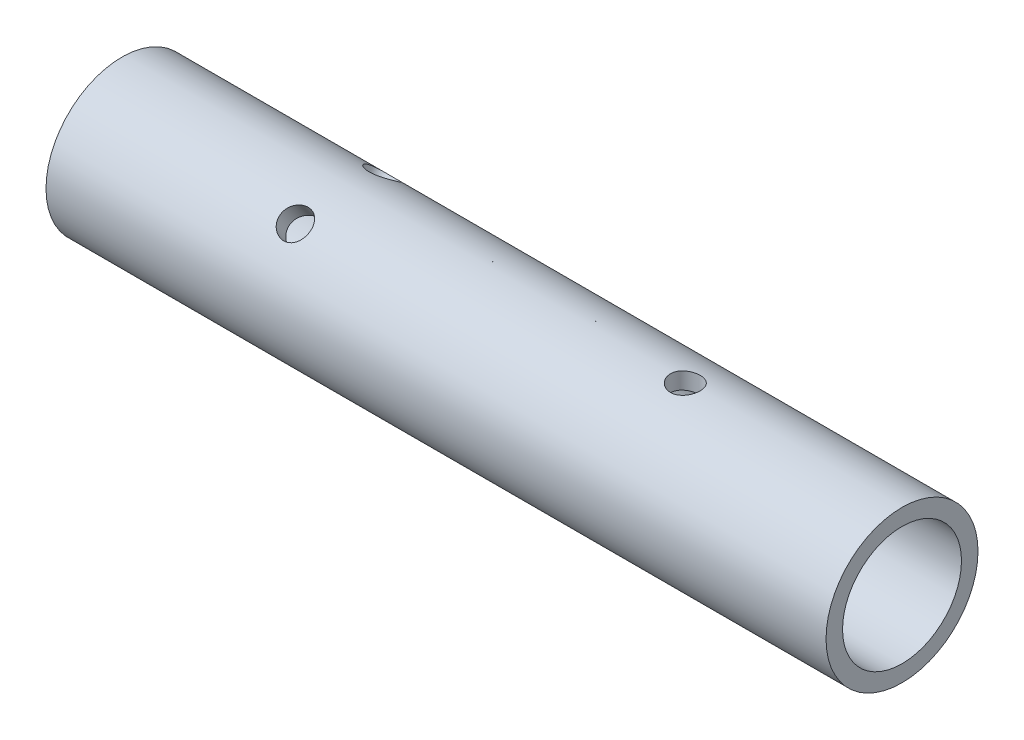
SolidWorks part; units mm, degrees
ref_plane "Front Plane" through (0, 0, 0) normal (0, 0, 1) x (1, 0, 0)
ref_plane "Top Plane" through (0, 0, 0) normal (0, 1, 0) x (1, 0, 0)
ref_plane "Right Plane" through (0, 0, 0) normal (1, 0, 0) x (0, 0, -1)
sketch "Sketch1" plane through (0, 0, 0) normal (1, 0, 0) x (0, 0, -1)
  circle A0 centre (0, 0) radius 16.7005
  circle A1 centre (0, 0) radius 13.0683
  dimension "D1" = 33.401
  dimension "D2" = 26.1366
extrude "Boss-Extrude1" add sketch "Sketch1" along normal blind 254
sketch "Sketch3" plane through (0, 0, 0) normal (0, 1, 0) x (1, 0, 0)
  line L0 (127, 16.7005) -> (127, -16.7005) construction
  line L1 (254, 16.7005) -> (0, 16.7005) construction
  line L2 (0, -16.7005) -> (254, -16.7005) construction
  circle A0 centre (127, 0) radius 3.2639
  dimension "D1" = 6.5278
extrude "Cut-Extrude2" cut sketch "Sketch3" against normal through all both and the other way through all
ref_axis "Axis1" through (254, 0, 0) along (-1, 0, 0)
ref_plane "Plane1" through (0, 0, 0) normal (0, 0.8192, -0.5736) x (-1, 0, 0)
sketch "Sketch4" plane through (0, 0, 0) normal (0, 0.8192, -0.5736) x (-1, 0, 0)
  line L0 (-254, 0) -> (-203.2, 0) construction
  line L1 (-254, 16.7005) -> (-254, -16.7005) construction
  line L2 (-254, 0) -> (0, 0) construction
  line L3 (0, 0) -> (-50.8, 0) construction
  circle A0 centre (-203.2, 0) radius 3.2639
  circle A1 centre (-50.8, 0) radius 3.2639
  dimension "D2" = 6.5278
  dimension "D1" = 50.8
extrude "Cut-Extrude3" cut sketch "Sketch4" against normal through all both and the other way through all
sketch "Sketch5" plane through (254, 0, 0) normal (1, 0, 0) x (0, 0, -1)
  circle A0 centre (0, 0) radius 16.7005 construction
  circle A1 centre (0, 0) radius 16.7005
extrude "Cut-Extrude4" cut sketch "Sketch5" against normal blind 79.375
mirror "Mirror1" about plane through (0, 0, 0) normal (0, 0, 1) of "Cut-Extrude3"
sketch "Sketch7" plane through (0, 0, 0) normal (-1, 0, 0) x (0, 0, 1)
  circle A1 centre (0, 0) radius 16.7005
  circle A2 centre (0, 0) radius 16.7005
  dimension "D1" = 0
extrude "Cut-Extrude6" cut sketch "Sketch7" against normal blind 3.175
